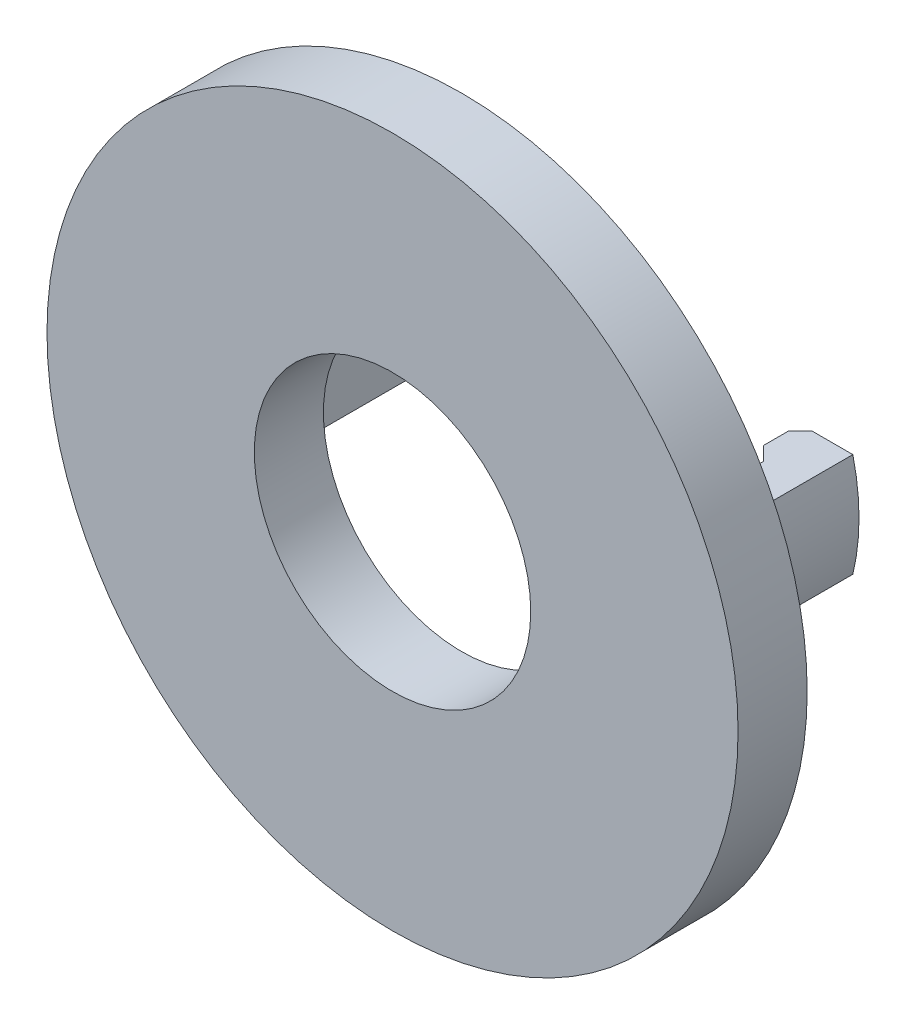
SolidWorks part; units mm, degrees
ref_plane "Front" through (0, 0, 0) normal (0, 0, 1) x (1, 0, 0)
ref_plane "Top" through (0, 0, 0) normal (0, 1, 0) x (1, 0, 0)
ref_plane "Right" through (0, 0, 0) normal (1, 0, 0) x (0, 0, -1)
sketch "Guard base" plane through (0, 0, 0) normal (0, 0, 1) x (1, 0, 0)
  circle A0 centre (0, 0) radius 25
  dimension "D1" = 50
extrude "Guard" add sketch "Guard base" along normal blind 5
sketch "Inner axle hole base" plane through (0, 0, 5) normal (0, 0, 1) x (1, 0, 0)
  circle A0 centre (0, 0) radius 10
  dimension "D1" = 20
extrude "Inner axle hole" cut sketch "Inner axle hole base" against normal through all
sketch "Coupling tooth base" plane through (0, 0, 0) normal (0, 1, 0) x (1, 0, 0)
  line L0 (10, 0) -> (15.5, 0) construction
  line L1 (15.5, 0) -> (15.5, 13)
  line L2 (12.5, 2.5) -> (12.5, 9) construction
  line L3 (15.5, 13) -> (12.5, 13) construction
  line L4 (12.5, 13) -> (11.5, 12) construction
  line L5 (11.5, 10) -> (12.5, 9) construction
  line L6 (16, 12.75) -> (16, 0)
  line L7 (12.75, 9.1036) -> (12.75, 2.3964)
  line L8 (12.5, 2.5) -> (10, 0) construction
  line L9 (12.75, 9.1036) -> (11.75, 10.1036)
  line L10 (11.5, 12) -> (11.5, 10) construction
  line L11 (11.75, 10.1036) -> (11.75, 11.8964)
  line L12 (15.5, 0) -> (15.5, 12.75) construction
  line L13 (15.5, 0) -> (10.3536, 0)
  line L14 (12.75, 2.3964) -> (10.3536, 0)
  line L15 (11.75, 11.8964) -> (12.6036, 12.75)
  line L16 (12.6036, 12.75) -> (15.5, 12.75)
  line L17 (15.5, 12.75) -> (25, 12.75)
  line L18 (25, 12.75) -> (25, 0)
  line L19 (25, 0) -> (15.5, 0)
  dimension "D2" = 1
  dimension "D3" = 4
  dimension "D4" = 13
  dimension "D5" = 4
  dimension "D6" = 0.25
  dimension "D7" = 0.25
  dimension "D8" = 0.25
  dimension "D9" = 0.25
  dimension "D10" = 225
  dimension "D11" = 5.5
  dimension "D12" = 0.25
  dimension "D13" = 135
  dimension "D14" = 0.25
  dimension "D15" = 0.5
extrude "Coupling tooth" add sketch "Coupling tooth base" along normal blind 3.75 and the other way blind 3.75 contours L16 L15 L11 L9 L7 L14 L13 L1 | L19 L6 L17 L1 region at (13.8475, 0, -6.2973) region at (15.75, 0, -6.375)
ref_axis "Center Z" through (0, 0, 0) along (0, 0, -1)
revolve "Circularity cut" cut sketch "Sketch6<4>" angle 360 about axis through (0, 0, 0) along (0, 0, -1) region at (20.5, 0, -6.375)
sketch "Sketch6<4>" plane through (0, 0, 0) normal (0, 1, 0) x (1, 0, 0) same geometry as "Coupling tooth base"
mirror "Coutpling teeth" about plane through (0, 0, 0) normal (1, 0, 0) of "Coupling tooth", "Circularity cut"
equation "\"mate_room\"= 0.25"
equation "\"D6@Coupling tooth base\"=\"mate_room\""
equation "\"D8@Coupling tooth base\"=\"mate_room\""
equation "\"D7@Coupling tooth base\"=\"mate_room\""
equation "\"D9@Coupling tooth base\"=\"mate_room\""
equation "\"D12@Coupling tooth base\"=\"mate_room\""
equation "\"D14@Coupling tooth base\"=\"mate_room\""
equation "\"removal_room\"= 0.75"
equation "\"large_inner_axle_diameter\"=20"
equation "\"D1@Inner axle hole base\"=\"large_inner_axle_diameter\""
equation "\"guard_thickness\"=5"
equation "\"spool_inner_diameter_room\"=1"
equation "\"32_92_coupling_tooth_height\"=13"
equation "\"32_92_coupling_tooth_thickness_total\"=4"
equation "\"32_92_coupling_tooth_protrusion\"=1"
equation "\"32_92_coupling_tooth_depth\"=8"
equation "\"32_92_coupling_tooth_base_thickness\"=5.5"
equation "\"D1@Guard\"=\"guard_thickness\""
equation "\"32_92_guard_diameter\"=50"
equation "\"D1@Guard base\"=\"32_92_guard_diameter\""
equation "\"D4@Coupling tooth base\"=\"32_92_coupling_tooth_height\""
equation "\"D3@Coupling tooth base\"=\"32_92_coupling_tooth_thickness_total\""
equation "\"D2@Coupling tooth base\"=\"32_92_coupling_tooth_protrusion\""
equation "\"D11@Coupling tooth base\"=\"32_92_coupling_tooth_base_thickness\""
equation "\"32_92_coupling_tooth_head_height\"=4"
equation "\"D5@Coupling tooth base\"=\"32_92_coupling_tooth_head_height\""
equation "\"32_92_spool_inner_diameter\"=32"
equation "\"32_92_spool_thickness\"=92"
